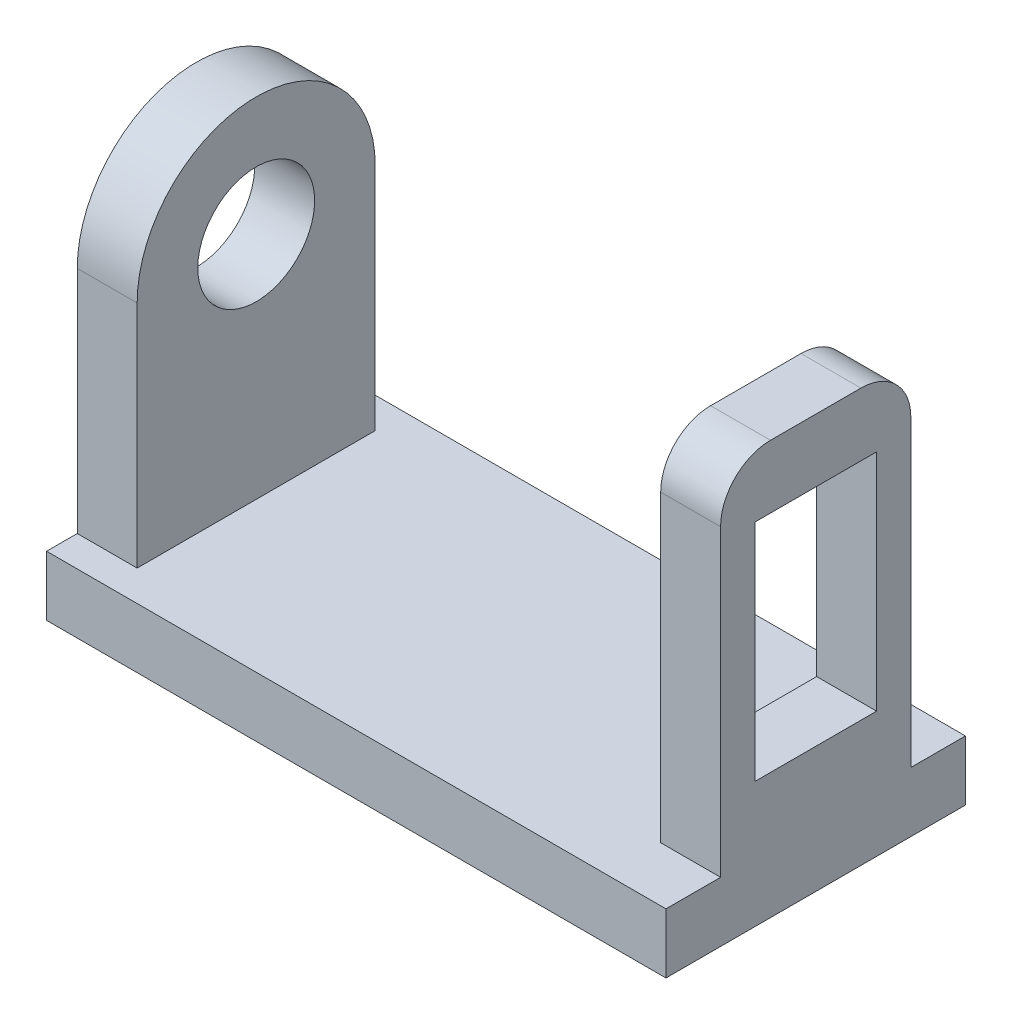
SolidWorks part; units mm, degrees
ref_plane "前视基准面" through (0, 0, 0) normal (0, 0, 1) x (1, 0, 0)
ref_plane "上视基准面" through (0, 0, 0) normal (0, 1, 0) x (1, 0, 0)
ref_plane "右视基准面" through (0, 0, 0) normal (1, 0, 0) x (0, 0, -1)
sketch "草图1" plane through (0, 0, 0) normal (0, 1, 0) x (1, 0, 0)
  line L0 (0, 0) -> (3.025, 0) construction
  line L1 (34.05, -15) -> (-28, -15)
  line L2 (34.05, -15) -> (34.05, 15)
  line L3 (34.05, 15) -> (-28, 15)
  line L4 (-28, -15) -> (-28, 15)
  line L5 (34.05, -15) -> (-28, 15) construction
  line L6 (34.05, 15) -> (-28, -15) construction
  point P0 (0, 0)
  point P6 (-43.3775, 35.8328)
  point P10 (47.7127, 22.3033)
  point P11 (0, 0)
  point P12 (0, 0)
  point P13 (21.5653, 3.4796)
  dimension "D1" = 28
  dimension "D2" = 34.05
  dimension "D3" = 30
extrude "凸台-拉伸1" add sketch "草图1" along normal blind 6
sketch "草图2" plane through (-28, 0, 0) normal (-1, 0, 0) x (0, 0, 1)
  line L0 (-15, 6) -> (15, 6) construction
  line L1 (11.9252, 40.9252) -> (-11.9252, 40.9252)
  line L2 (11.9252, 40.9252) -> (11.9252, 6)
  line L3 (11.9252, 6) -> (-11.9252, 6)
  line L4 (-11.9252, 40.9252) -> (-11.9252, 6)
  line L5 (11.9252, 40.9252) -> (-11.9252, 6) construction
  line L6 (11.9252, 6) -> (-11.9252, 40.9252) construction
  line L7 (0, 23.4626) -> (0, 6) construction
  circle A0 centre (0, 29) radius 5.8528
  circle A1 centre (0, 29) radius 11.9252 construction
  point P0 (0, 23.4626)
  dimension "D1" = 23
extrude "凸台-拉伸2" add sketch "草图2" against normal blind 6
fillet "圆角1" 2 edges at (-25, 40.9252, -11.9252) (-25, 40.9252, 11.9252) type full round first side face at (-25, 23.4626, -11.9252) second side face at (-25, 23.4626, 11.9252) middle face at (-25, 40.9252, 0)
sketch "草图3" plane through (34.05, 0, 0) normal (1, 0, 0) x (0, 0, -1)
  line L1 (9.5285, 41.4153) -> (-9.5285, 41.4153)
  line L2 (9.5285, 41.4153) -> (9.5285, 6)
  line L3 (9.5285, 6) -> (-9.5285, 6)
  line L4 (-9.5285, 41.4153) -> (-9.5285, 6)
  line L5 (9.5285, 41.4153) -> (-9.5285, 6) construction
  line L6 (9.5285, 6) -> (-9.5285, 41.4153) construction
  line L7 (0, 23.85) -> (0, 0) construction
  line L8 (6.1, 35.1) -> (-6.1, 35.1)
  line L9 (6.1, 35.1) -> (6.1, 12.6)
  line L10 (6.1, 12.6) -> (-6.1, 12.6)
  line L11 (-6.1, 35.1) -> (-6.1, 12.6)
  line L12 (6.1, 35.1) -> (-6.1, 12.6) construction
  line L13 (6.1, 12.6) -> (-6.1, 35.1) construction
  line L17 (-15, 6) -> (15, 6) construction
  circle A0 centre (0, 29) radius 5.8528 construction
  circle A1 centre (0, 29) radius 5.8528 construction
  point P0 (0, 23.7076)
  point P7 (0, 23.85)
  point P18 (0, 0)
  point P19 (-10.9215, 43.0779)
  point P22 (0, 0)
  dimension "D1" = 22.5
  dimension "D2" = 12.2
  dimension "D3" = 6.1
extrude "凸台-拉伸3" add sketch "草图3" against normal blind 6
fillet "圆角2" radius 5 2 edges at (31.05, 41.4153, 9.5285) (31.05, 41.4153, -9.5285)
